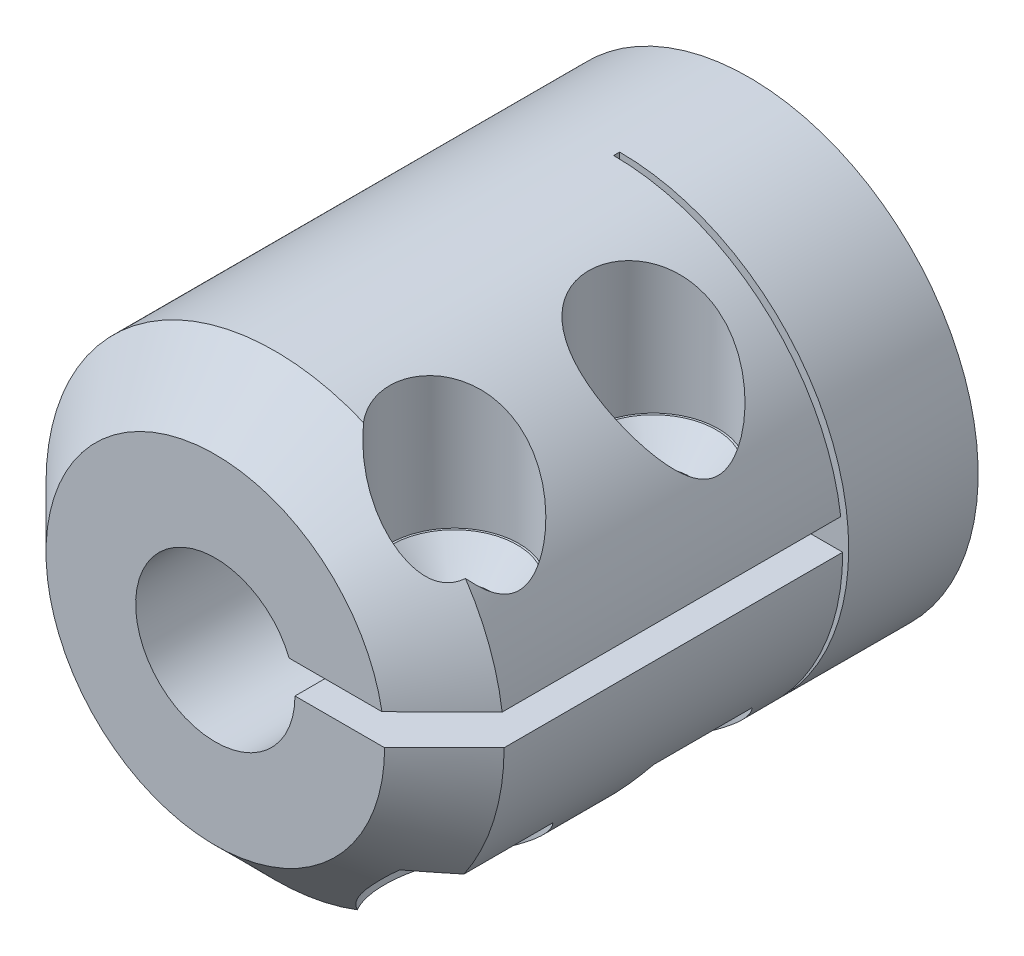
SolidWorks part; units mm, degrees
ref_plane "Płaszczyzna przednia" through (0, 0, 0) normal (0, 0, 1) x (1, 0, 0)
ref_plane "Płaszczyzna górna" through (0, 0, 0) normal (0, 1, 0) x (1, 0, 0)
ref_plane "Płaszczyzna prawa" through (0, 0, 0) normal (1, 0, 0) x (0, 0, -1)
sketch "Szkic1" plane through (0, 0, 0) normal (0, 0, 1) x (1, 0, 0)
  circle A0 centre (0, 0) radius 4
  circle A1 centre (0, 0) radius 11.5
  dimension "D1" = 8
  dimension "D2" = 23
extrude "Dodanie-wyciągnięcie1" add sketch "Szkic1" along normal blind 20
sketch "Szkic2" plane through (0, 0, 20) normal (0, 0, 1) x (1, 0, 0)
  line L0 (0, 0) -> (0, -1) construction
  line L1 (7, 4) -> (4, 4)
  line L2 (5.5, 4) -> (8.5, 4)
  line L3 (5.5, 4) -> (5.5, -6)
  line L4 (5.5, -6) -> (8.5, -6)
  line L5 (8.5, 4) -> (8.5, -6)
  line L6 (5.5, 4) -> (8.5, -6) construction
  line L7 (5.5, -6) -> (8.5, 4) construction
  line L8 (4, 4) -> (5.5, 1.5)
  line L9 (7, 4) -> (10, 4)
  line L10 (10, 4) -> (8.5, 1.5)
  line L11 (0, -1) -> (7, -1) construction
  line L12 (7, -1) -> (7, -5.1625) construction
  line L14 (4.9, -1) -> (9.1, -1)
  line L15 (4.9, -1) -> (4.9, -6)
  line L16 (4.9, -6) -> (9.1, -6)
  line L17 (9.1, -1) -> (9.1, -6)
  line L18 (4.9, -1) -> (9.1, -6) construction
  line L19 (4.9, -6) -> (9.1, -1) construction
  point P3 (7, -1)
  point P13 (7, -3.5)
  dimension "D1" = 10
  dimension "D2" = 3
  dimension "D3" = 6
  dimension "D4" = 2.5
  dimension "D5" = 1
  dimension "D6" = 7
  dimension "D7" = 4.2
  dimension "D8" = 5
sketch "Szkic3" plane through (0, 0, 0) normal (0, 1, 0) x (1, 0, 0)
  line L1 (0, 0) -> (11.5, 0)
  line L2 (0, 0) -> (0, -20)
  line L3 (0, -20) -> (11.5, -20)
  line L4 (11.5, 0) -> (11.5, -20)
extrude "Wytnij-wyciągnięcie1" cut sketch "Szkic3" along normal blind 1.5
ref_plane "Płaszczyzna1" through (0, 4, 0) normal (0, 1, 0) x (1, 0, 0)
sketch "Szkic4" plane through (0, 4, 0) normal (0, 1, 0) x (1, 0, 0)
  line L0 (7, -20) -> (7, 0)
  line L1 (11.4018, 0) -> (3.7081, 0) construction
  line L2 (7, -10) -> (7, -20) construction
  line L3 (7, -10) -> (-15.8022, -10) construction
  circle A0 centre (7, -15) radius 3.25
  circle A1 centre (7, -5) radius 3.25
  dimension "D1" = 6.5
  dimension "D2" = 10
extrude "Wytnij-wyciągnięcie2" cut sketch "Szkic4" along normal blind 32 contours L0 A0 | A1 L0 | A1 L0 | L0 A0 region at (5.6207, 4, 15) region at (5.6207, 4, 5) region at (8.3793, 4, 5) region at (8.3793, 4, 15)
hole_wizard "Pogłębienie stożkowe pod M3 Wkręt z łbem płaskim1" positions "Szkic 3D1" profile "Szkic5" countersink size "M3" standard "DIN" end condition through all
sketch3d "Szkic 3D1"
  line L0 (7, 8.4547, 15) -> (7, 4, 15) construction
  line L1 (7, 8.4627, 5) -> (7, 4, 5) construction
  point P0 (7, 4, 15)
  point P4 (7, 4, 5)
sketch "Szkic5" plane through (7, 4, 15) normal (1, 0, 0) x (0, 0, 1)
  line L0 (0, 0) -> (0, 15.5)
  line L1 (0, 15.5) -> (1.8, 15.5)
  line L2 (1.8, 15.5) -> (1.8, 1.35)
  line L3 (1.8, 1.35) -> (3.15, 0)
  line L5 (3.15, 0) -> (0, 0)
  line L6 (-1.8, 1.35) -> (-3.15, 0) construction
  line L11 (0, -6.35) -> (0, 107.95) construction
  dimension "Średnica otworu na wylot" = 3.6
  dimension "Głębokość otworu na wylot" = 15.5
  dimension "Średnica zewnętrznego pogłębienia stożkowego" = 6.3
  dimension "Kąt zewnętrznego pogłębienia stożkowego" = 90
ref_plane "Płaszczyzna2" through (0, -6.5, 0) normal (0, -1, 0) x (-1, 0, 0)
sketch "Szkic7" plane through (0, -6.5, 0) normal (0, -1, 0) x (-1, 0, 0)
  line L0 (-11.5, -10) -> (11.5, -10) construction
  line L1 (-11.5, -20) -> (-11.5, 0) construction
  line L2 (11.5, -20) -> (11.5, 0) construction
  circle A0 centre (-7, -5) radius 3.5
  circle A1 centre (-7, -15) radius 3.5
  dimension "D1" = 7
extrude "Wytnij-wyciągnięcie3" cut sketch "Szkic7" along normal blind 32
sketch "Szkic8" plane through (0, -6.5, 0) normal (0, -1, 0) x (1, 0, 0)
  line L0 (11.5, 10) -> (-11.5, 10) construction
  line L1 (11.5, 20) -> (11.5, 0) construction
  line L2 (-11.5, 20) -> (-11.5, 0) construction
  circle A0 centre (7, 15) radius 2
  circle A1 centre (7, 5) radius 2
  dimension "D1" = 4
extrude "Wytnij-wyciągnięcie4" cut sketch "Szkic8" against normal blind 7 contours A0 | A1
sketch "Szkic9" plane through (0, 0, 0) normal (0, 0, -1) x (-1, 0, 0)
  line L0 (0, 0) -> (0, 12.2687)
  line L1 (0, 0) -> (0, -12.6536)
  line L4 (-11.4018, 1.5) -> (-3.7081, 1.5)
  line L5 (-4, 0) -> (-11.5, 0)
  line L6 (-11.4018, 1.5) -> (-3.7081, 1.5)
  line L7 (-4, 0) -> (-11.5, 0)
  arc A2 (-11.5, 0) -> (-11.4018, 1.5) centre (0, 0) ccw
  arc A3 (-4, 0) -> (-3.7081, 1.5) centre (0, 0) ccw
  arc A4 (-11.5, 0) -> (-11.4018, 1.5) centre (0, 0) ccw
  arc A5 (-4, 0) -> (-3.7081, 1.5) centre (0, 0) ccw
  arc M5 (-11.5, 0) -> (-11.4018, 1.5) centre (0, 0) ccw
  arc M7 (-3.7081, 1.5) -> (-4, 0) centre (0, 0) cw
  dimension "D1" = 0
extrude "Dodanie-wyciągnięcie2" add sketch "Szkic9" along normal blind 0.3 contours L1 L0 M7 M5 region at (-5.3189, 0, 0)
sketch "Szkic10" plane through (0, 0, -0.3) normal (0, 0, -1) x (-1, 0, 0)
  circle A0 centre (0, 0) radius 11.5
extrude "Dodanie-wyciągnięcie3" add sketch "Szkic10" along normal blind 1.5
sketch "Szkic11" plane through (0, 0, -1.8) normal (0, 0, -1) x (-1, 0, 0)
  line L1 (-5, 5) -> (5, 5)
  line L2 (-5, 5) -> (-5, -5)
  line L3 (-5, -5) -> (5, -5)
  line L4 (5, 5) -> (5, -5)
  line L5 (-5, 5) -> (5, -5) construction
  line L6 (-5, -5) -> (5, 5) construction
  circle A0 centre (0, 0) radius 11.5
  dimension "D1" = 10
extrude "Dodanie-wyciągnięcie4" add sketch "Szkic11" along normal blind 5
chamfer "Sfazowanie1" distance 3 angle 45 1 edges at (-11.4754, -0.7516, 20)
